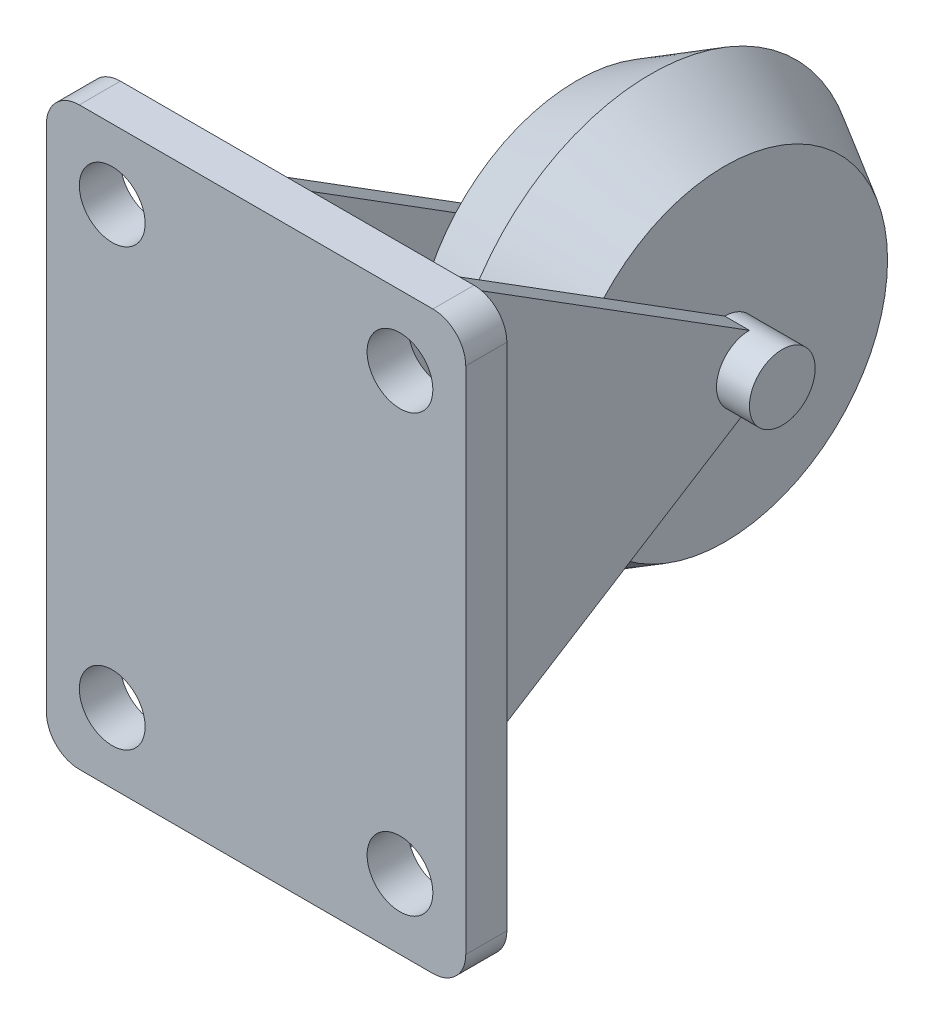
SolidWorks part; units mm, degrees
ref_plane "前视基准面" through (0, 0, 0) normal (0, 0, 1) x (1, 0, 0)
ref_plane "上视基准面" through (0, 0, 0) normal (0, 1, 0) x (1, 0, 0)
ref_plane "右视基准面" through (0, 0, 0) normal (1, 0, 0) x (0, 0, -1)
sketch "草图1" plane through (0, 0, 0) normal (0, 0, 1) x (1, 0, 0)
  line L1 (21.5, -35) -> (-21.5, -35)
  line L2 (25.5, -31) -> (25.5, 31)
  line L3 (21.5, 35) -> (-21.5, 35)
  line L4 (-25.5, -31) -> (-25.5, 31)
  line L5 (25.5, -35) -> (-25.5, 35) construction
  line L6 (25.5, 35) -> (-25.5, -35) construction
  line L7 (17.5, -26.5) -> (-17.5, -26.5) construction
  line L8 (17.5, -26.5) -> (17.5, 26.5) construction
  line L9 (17.5, 26.5) -> (-17.5, 26.5) construction
  line L10 (-17.5, -26.5) -> (-17.5, 26.5) construction
  line L11 (17.5, -26.5) -> (-17.5, 26.5) construction
  line L12 (17.5, 26.5) -> (-17.5, -26.5) construction
  circle A0 centre (-17.5, 26.5) radius 4
  circle A1 centre (17.5, 26.5) radius 4
  circle A2 centre (17.5, -26.5) radius 4
  circle A3 centre (-17.5, -26.5) radius 4
  arc A4 (-21.5, -35) -> (-25.5, -31) centre (-21.5, -31) cw
  arc A5 (21.5, -35) -> (25.5, -31) centre (21.5, -31) ccw
  arc A6 (25.5, 31) -> (21.5, 35) centre (21.5, 31) ccw
  arc A7 (-25.5, 31) -> (-21.5, 35) centre (-21.5, 31) cw
  point P0 (0, 0)
  point P6 (0, 0)
  dimension "D5" = 8
  dimension "D6" = 8
  dimension "D7" = 8
  dimension "D8" = 8
  dimension "D9" = 4
  dimension "D1" = 70
  dimension "D2" = 51
  dimension "D3" = 53
  dimension "D4" = 35
extrude "凸台-拉伸1" add sketch "草图1" along normal blind 5
sketch "草图2" plane through (0, 0, 0) normal (1, 0, 0) x (0, 0, -1)
  line L0 (49.3902, 0) -> (-2.8498, 0) construction
  line L5 (-5, 31) -> (68, 31) construction
  line L6 (-5, 31) -> (-5, -31)
  line L7 (-5, -31) -> (68, -31) construction
  line L8 (68, 31) -> (68, -31) construction
  line L9 (43, 4) -> (0, 31)
  line L10 (43, -4) -> (0, -31)
  line L11 (0, 31) -> (0, -31)
  circle A0 centre (43, 0) radius 25
  circle A1 centre (43, 0) radius 4
  dimension "D3" = 50
  dimension "D4" = 8
  dimension "D1" = 73
  dimension "D2" = 62
extrude "凸台-拉伸2" add sketch "草图2" along normal blind 12 and the other way blind 12 contours A0 L9 L11 L10 | A1 L9 A0 L10 region at (0, 0, -28.3555) region at (0, 0, -9.2568)
extrude "凸台-拉伸3" add sketch "草图2<3>" along normal blind 16 and the other way blind 16 contours A1 region at (0, 0, -43)
sketch "草图2<3>" plane through (0, 0, 0) normal (1, 0, 0) x (0, 0, -1) same geometry as "草图2"
extrude "切除-拉伸1" cut sketch "草图2<4>" against normal blind 9 and the other way blind 9 contours A0 L9 L11 L10 | A1 L9 A0 L10 | A1 region at (0, 0, -28.3555) region at (0, 0, -43) region at (0, 0, -9.2568)
sketch "草图2<4>" plane through (0, 0, 0) normal (1, 0, 0) x (0, 0, -1) same geometry as "草图2"
extrude "凸台-拉伸4" add sketch "草图2<5>" along normal blind 9 draft 30 and the other way blind 9 draft 30 contours A0
sketch "草图2<5>" plane through (0, 0, 0) normal (1, 0, 0) x (0, 0, -1) same geometry as "草图2"
